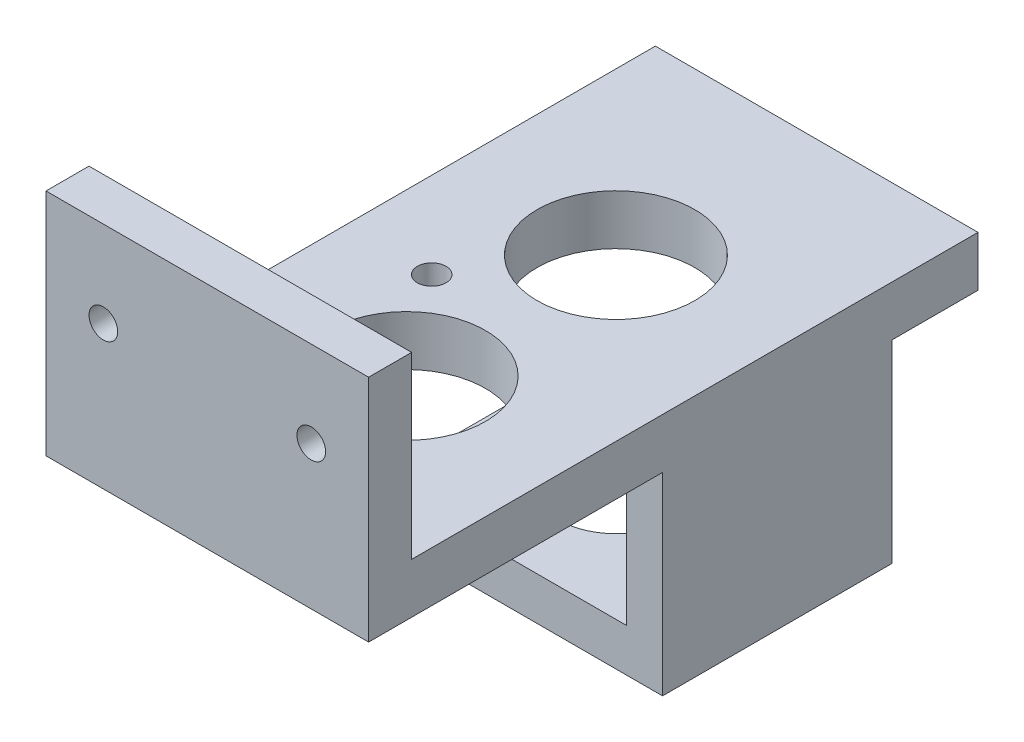
SolidWorks part; units mm, degrees
ref_plane "Front Plane" through (0, 0, 0) normal (0, 0, 1) x (1, 0, 0)
ref_plane "Top Plane" through (0, 0, 0) normal (0, 1, 0) x (1, 0, 0)
ref_plane "Right Plane" through (0, 0, 0) normal (1, 0, 0) x (0, 0, -1)
sketch "Sketch1" plane through (0, 0, 0) normal (0, 1, 0) x (1, 0, 0)
  line L1 (-50.1619, 28.7652) -> (-5.1619, 28.7652)
  line L2 (-50.1619, 28.7652) -> (-50.1619, -56.2348)
  line L3 (-50.1619, -56.2348) -> (-5.1619, -56.2348)
  line L4 (-5.1619, 28.7652) -> (-5.1619, -56.2348)
  dimension "D1" = 85
  dimension "D2" = 45
extrude "Boss-Extrude1" add sketch "Sketch1" along normal blind 7
sketch "Sketch2" plane through (0, 7, 0) normal (0, 1, 0) x (1, 0, 0)
  line L0 (-50.1619, -56.2348) -> (-5.1619, -56.2348) construction
  line L1 (-50.1619, 28.7652) -> (-50.1619, -56.2348) construction
  circle A0 centre (-27.6619, 0.7652) radius 11
  dimension "D1" = 22
  dimension "D2" = 57
  dimension "D3" = 22.5
extrude "Cut-Extrude1" cut sketch "Sketch2" against normal blind 100
sketch "Sketch3" plane through (0, 7, 0) normal (0, 1, 0) x (1, 0, 0)
  line L0 (-50.1619, 28.7652) -> (-50.1619, -56.2348) construction
  circle A0 centre (-27.6619, -28.4348) radius 11
  circle A1 centre (-27.6619, 0.7652) radius 11 construction
  dimension "D1" = 22
  dimension "D2" = 29.2
  dimension "D3" = 22.5
extrude "Cut-Extrude2" cut sketch "Sketch3" against normal blind 7
sketch "Sketch4" plane through (0, 7, 0) normal (0, 1, 0) x (1, 0, 0)
  line L0 (-5.1619, -56.2348) -> (-5.1619, 28.7652) construction
  line L1 (-50.1619, -56.2348) -> (-5.1619, -56.2348)
  line L2 (-50.1619, -56.2348) -> (-50.1619, -50.2348)
  line L3 (-50.1619, -50.2348) -> (-5.1619, -50.2348)
  line L4 (-5.1619, -56.2348) -> (-5.1619, -50.2348)
  dimension "D1" = 6
extrude "Boss-Extrude3" add sketch "Sketch4" along normal blind 25
sketch "Sketch5" plane through (0, 0, 50.2348) normal (0, 0, -1) x (-1, 0, 0)
  line L0 (50.1619, 32) -> (50.1619, 7) construction
  line L1 (5.1619, 32) -> (50.1619, 32) construction
  circle A0 centre (42.1619, 20) radius 2
  circle A1 centre (13.1619, 20) radius 2
  dimension "D1" = 4
  dimension "D2" = 4
  dimension "D3" = 8
  dimension "D4" = 29
  dimension "D5" = 0
  dimension "D6" = 12
extrude "Cut-Extrude3" cut sketch "Sketch5" against normal blind 14
sketch "Sketch6" plane through (0, 7, 0) normal (0, 1, 0) x (1, 0, 0)
  circle A0 centre (-38.1619, -14.4348) radius 2
  circle A1 centre (-38.1619, -42.4348) radius 2
  circle A2 centre (-27.6619, -28.4348) radius 11 construction
  dimension "D1" = 4
  dimension "D2" = 4
  dimension "D3" = 28
  dimension "D4" = 10.5
  dimension "D5" = 14
extrude "Cut-Extrude4" cut sketch "Sketch6" against normal blind 14
sketch "Sketch7" plane through (0, 0, 0) normal (0, -1, 0) x (1, 0, 0)
  line L0 (-5.1619, 56.2348) -> (-5.1619, -28.7652) construction
  line L1 (-5.1619, -16.7652) -> (-10.1619, -16.7652)
  line L2 (-5.1619, -16.7652) -> (-5.1619, 15.2348)
  line L3 (-5.1619, 15.2348) -> (-10.1619, 15.2348)
  line L4 (-10.1619, -16.7652) -> (-10.1619, 15.2348)
  circle A0 centre (-27.6619, -0.7652) radius 11 construction
  dimension "D1" = 16
  dimension "D2" = 16
  dimension "D3" = 5
extrude "Boss-Extrude4" add sketch "Sketch7" along normal blind 27
sketch "Sketch8" plane through (-10.1619, 0, 0) normal (-1, 0, 0) x (0, 0, 1)
  line L0 (15.2348, -27) -> (15.2348, 0) construction
  line L1 (-16.7652, -27) -> (15.2348, -27)
  line L2 (-16.7652, -27) -> (-16.7652, -21)
  line L3 (-16.7652, -21) -> (15.2348, -21)
  line L4 (15.2348, -27) -> (15.2348, -21)
  dimension "D1" = 6
extrude "Boss-Extrude5" add sketch "Sketch8" along normal blind 35
sketch "Sketch9" plane through (0, 7, 0) normal (0, 1, 0) x (1, 0, 0)
  circle A2 centre (-27.6619, 0.7652) radius 8
  circle A3 centre (-27.6619, 0.7652) radius 11 construction
  dimension "D1" = 16
  dimension "D2" = 0
extrude "Cut-Extrude6" cut sketch "Sketch9" against normal blind 50
